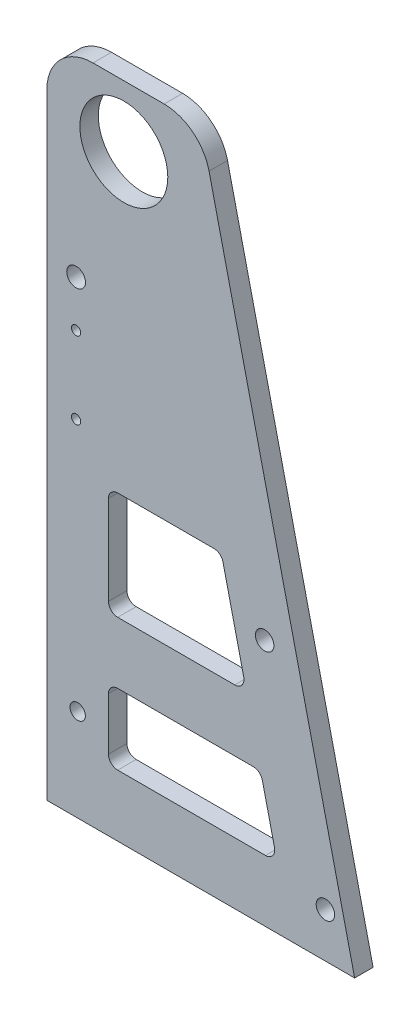
SolidWorks part; units mm, degrees
material "Policarbonato"
ref_plane "Plano frontal" through (0, 0, 0) normal (0, 0, 1) x (1, 0, 0)
ref_plane "Plano superior" through (0, 0, 0) normal (0, 1, 0) x (1, 0, 0)
ref_plane "Plano direito" through (0, 0, 0) normal (1, 0, 0) x (0, 0, -1)
sketch "Esboço1" plane through (0, 0, 0) normal (0, 0, 1) x (1, 0, 0)
  line L0 (0, 0) -> (0, 215)
  line L2 (100, 0) -> (0, 0)
  line L3 (0, 215) -> (50, 215)
  line L4 (50, 215) -> (100, 0)
  line L5 (10, 103) -> (10, 15) construction
  line L6 (25, 215) -> (25, 175) construction
  line L7 (10, 15) -> (75.7552, 15) construction
  line L8 (75.7552, 15) -> (55.2901, 103) construction
  line L9 (55.2901, 103) -> (10, 103) construction
  line L10 (20, 95) -> (20, 66)
  line L11 (23, 63) -> (61.0374, 63)
  line L12 (63.9594, 66.6795) -> (57.2152, 95.6795)
  line L13 (54.2932, 98) -> (23, 98)
  line L14 (20, 40) -> (20, 23)
  line L15 (23, 20) -> (71.0374, 20)
  line L16 (73.9594, 23.6795) -> (70.0059, 40.6795)
  line L17 (23, 43) -> (67.0839, 43)
  line L18 (0, 195) -> (50, 195) construction
  line L23 (17, 205) -> (33, 185) construction
  line L24 (17, 185) -> (33, 205) construction
  arc A8 (70.0059, 40.6795) -> (67.0839, 43) centre (67.0839, 40) ccw
  arc A9 (71.0374, 20) -> (73.9594, 23.6795) centre (71.0374, 23) ccw
  arc A10 (20, 23) -> (23, 20) centre (23, 23) ccw
  arc A11 (20, 40) -> (23, 43) centre (23, 40) cw
  arc A12 (57.2152, 95.6795) -> (54.2932, 98) centre (54.2932, 95) ccw
  arc A13 (61.0374, 63) -> (63.9594, 66.6795) centre (61.0374, 66) ccw
  arc A14 (20, 66) -> (23, 63) centre (23, 66) ccw
  arc A15 (20, 95) -> (23, 98) centre (23, 95) cw
  circle A20 centre (25, 195) radius 14.2875
  circle A21 centre (10, 30) radius 2.5
  point P8 (25, 195)
  point P49 (20, 63)
  dimension "D3" = 20
  dimension "D4" = 16
  dimension "D7" = 28.575
  dimension "D21" = 3
  dimension "D20" = 10
  dimension "D22" = 5
  dimension "D1" = 215
  dimension "D2" = 100
  dimension "D5" = 50
  dimension "D9" = 20
  dimension "D10" = 20
  dimension "D11" = 10
  dimension "D12" = 20
  dimension "D13" = 15
  dimension "D14" = 20
  dimension "D15" = 10
  dimension "D16" = 29
  dimension "D17" = 17
  dimension "D18" = 10
  dimension "D19" = 30
  dimension "D8" = 20
extrude "Ressalto-extrusão2" add sketch "Esboço1" along normal blind 6
fillet "Filete1" radius 15 2 edges at (0, 215, 3) (50, 215, 3)
sketch "Esboço3" plane through (0, 0, 0) normal (0, 0, -1) x (-1, 0, 0)
  line L1 (0, 0) -> (-100, 0) construction
  line L2 (0, 200) -> (0, 0) construction
  circle A0 centre (-9.5, 112) radius 1.5
  circle A1 centre (-90.5, 14.5) radius 3
  circle A2 centre (-9.5, 137) radius 1.5
  circle A3 centre (-9.5, 152) radius 3.05
  point P6 (-9.5, 112)
  point P9 (-9.5, 137)
  dimension "D5" = 6
  dimension "D1" = 25
  dimension "D6" = 3
  dimension "D7" = 112
  dimension "D8" = 15
  dimension "D9" = 6.1
  dimension "D2" = 9.5
  dimension "D3" = 14.5
  dimension "D4" = 9.5
extrude "Corte-extrusão1" cut sketch "Esboço3" against normal through all
sketch "Esboço5" plane through (0, 0, 0) normal (0, 0, -1) x (-1, 0, 0)
  circle A1 centre (-70.7598, 80.3986) radius 3
extrude "Corte-extrusão2" cut sketch "Esboço5" against normal through all
